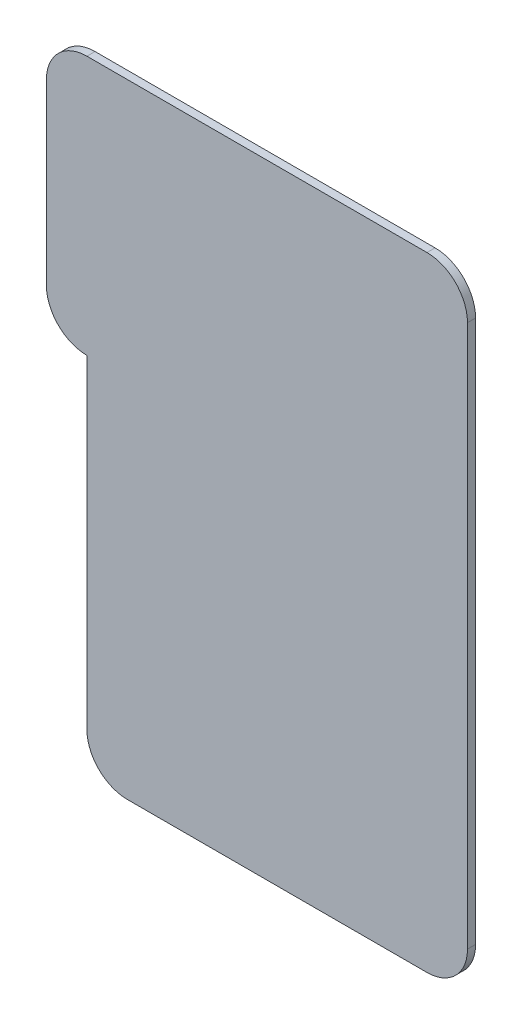
SolidWorks part; units mm, degrees
material "Galvanized Steel"
ref_plane "Front Plane" through (0, 0, 0) normal (0, 0, 1) x (1, 0, 0)
ref_plane "Top Plane" through (0, 0, 0) normal (0, 1, 0) x (1, 0, 0)
ref_plane "Right Plane" through (0, 0, 0) normal (1, 0, 0) x (0, 0, -1)
sketch "Sketch1" plane through (0, 0, 0) normal (0, 0, 1) x (1, 0, 0)
  line L0 (-65, 15) -> (-75, 15)
  line L1 (29, -75) -> (-65, -75)
  line L2 (29, -75) -> (29, 79)
  line L3 (29, 79) -> (-75, 79)
  line L4 (-65, -75) -> (-65, 15)
  line L8 (-75, 15) -> (-75, 79)
  point P0 (-21, -30)
  dimension "D1" = 50
  dimension "D2" = 154
  dimension "D3" = 90
  dimension "D4" = 75
  dimension "D7" = 104
  dimension "D8" = 94
base flange "Base-Flange1" sketch "Sketch1" thickness 2 reverse thickness direction no parameters "D1"=0.7366
fillet "Fillet1" radius 10 5 edges at (-75, 79, -1) (-75, 15, -1) (-65, -75, -1) (29, -75, -1) (29, 79, -1)
sketch "Bend-Lines1" [suppressed] plane through (0, 0, 0) normal (0, 1, 0) x (1, 0, 0)
sketch "Bounding-Box1" [suppressed] plane through (0, 0, 0) normal (0, 1, 0) x (1, 0, 0)
sheet metal parameters "Sheet-Metal1" thickness 2 parameters "D1"=0.7366
flat pattern "Flat-Pattern1" [suppressed]
sketch "Bend-Lines2" plane through (0, 0, 0) normal (0, 1, 0) x (1, 0, 0)
sketch3d "Bounding-Box2" [suppressed]
  line L0 (29, 79, 0) -> (29, -75, 0) construction
  line L1 (-75, 79, 0) -> (-75, -75, 0) construction
  line L2 (29, 79, 0) -> (-75, 79, 0) construction
  line L3 (29, -75, 0) -> (-75, -75, 0) construction
